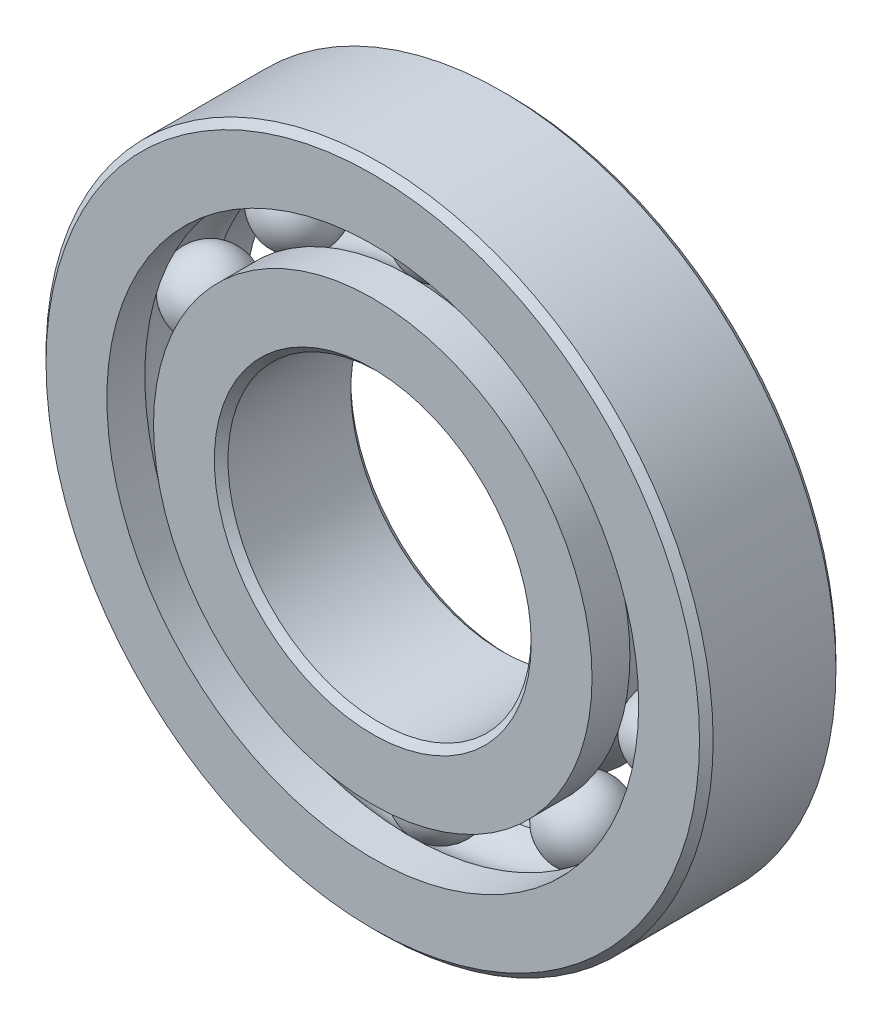
SolidWorks part; units mm, degrees
ref_plane "Front Plane" through (0, 0, 0) normal (0, 0, 1) x (1, 0, 0)
ref_plane "Top Plane" through (0, 0, 0) normal (0, 1, 0) x (1, 0, 0)
ref_plane "Right Plane" through (0, 0, 0) normal (1, 0, 0) x (0, 0, -1)
sketch "Sketch1" plane through (0, 0, 0) normal (1, 0, 0) x (0, 0, -1)
  line L0 (-3.5719, 0) -> (3.5719, 0) construction
  line L1 (0, 17.4625) -> (0, -17.4625) construction
  line L2 (3.2147, 17.4625) -> (-3.2147, 17.4625)
  line L3 (-3.2147, 17.4625) -> (-3.5719, 17.1053)
  line L4 (-3.5719, 17.1053) -> (-3.5719, 13.9212)
  line L5 (-3.5719, 13.9212) -> (-1.5875, 13.9212)
  line L6 (3.5719, 13.9212) -> (1.5875, 13.9212)
  line L7 (3.5719, 17.1053) -> (3.5719, 13.9212)
  line L8 (3.2147, 17.4625) -> (3.5719, 17.1053)
  line L9 (0, 17.4625) -> (0, 12.7) construction
  line L10 (0, 12.7) -> (0, 7.9375) construction
  arc A0 (-1.5875, 13.9212) -> (1.5875, 13.9212) centre (0, 12.7) cw
  point P14 (0, 7.9375)
  dimension "D3" = 3.175
  dimension "D1" = 45
  dimension "Width" = 7.1437
  dimension "OD" = 34.925
  dimension "D2" = 0.3572
  dimension "Shaft Dia" = 15.875
  dimension "D4" = 1.2212
revolve "Revolve1" add sketch "Sketch1" angle 360 about L0
sketch "Sketch3" plane through (0, 0, 0) normal (1, 0, 0) x (0, 0, -1)
  line L0 (-3.5719, 11.4788) -> (-1.5875, 11.4788)
  line L1 (0, 17.4625) -> (0, -17.4625) construction
  line L2 (-3.5719, 17.1053) -> (-3.5719, 13.9212) construction
  line L3 (-3.5719, 11.4788) -> (-3.5719, 8.2947)
  line L4 (-3.2147, 17.4625) -> (-3.5719, 17.1053) construction
  line L5 (-3.5719, 8.2947) -> (-3.2147, 7.9375)
  line L6 (-3.2147, 7.9375) -> (3.2147, 7.9375)
  line L7 (3.2147, 17.4625) -> (3.2147, -17.4625) construction
  line L8 (3.2147, 7.9375) -> (3.5719, 8.2947)
  line L9 (3.5719, -17.1053) -> (3.5719, 17.1053) construction
  line L10 (3.5719, 8.2947) -> (3.5719, 11.4788)
  line L11 (3.5719, 11.4788) -> (1.5875, 11.4788)
  line L13 (3.2147, 17.4625) -> (3.5719, 17.1053) construction
  arc A0 (1.5875, 13.9212) -> (-1.5875, 13.9212) centre (0, 12.7) ccw construction
  arc A1 (1.5875, 11.4788) -> (-1.5875, 11.4788) centre (0, 12.7) cw
revolve "Revolve3" add sketch "Sketch3" angle 360 about L0
sketch "Sketch4" plane through (0, 0, 0) normal (1, 0, 0) x (0, 0, -1)
  line L0 (-2.0028, 12.7) -> (2.0028, 12.7)
  arc A2 (-2.0028, 12.7) -> (2.0028, 12.7) centre (0, 12.7) cw
  arc A3 (1.5875, 13.9212) -> (-1.5875, 13.9212) centre (0, 12.7) ccw construction
revolve "Revolve4" add sketch "Sketch4" angle 360 about L0
ref_axis "Axis1" through (0, 0, -3.5719) along (0, 0, 1)
pattern_circular "CirPattern1" count 10 every 36 about axis through (0, 0, -3.5719) along (0, 0, 1) of bodies 104
sketch "Sketch5" plane through (0, 0, 0) normal (1, 0, 0) x (0, 0, -1)
  line L0 (-3.5719, 13.9212) -> (-1.5875, 13.9212) construction
  line L1 (-3.3933, 13.9212) -> (-2.0028, 13.9212)
  line L2 (-3.3933, 13.9212) -> (-3.3933, 11.4788)
  line L3 (-3.3933, 11.4788) -> (-2.0028, 11.4788)
  line L4 (-2.0028, 13.9212) -> (-2.0028, 11.4788)
  line L5 (-3.5719, 11.4788) -> (-1.5875, 11.4788) construction
  line L6 (3.5719, 13.9212) -> (1.5875, 13.9212) construction
  line L7 (3.3933, 13.9212) -> (2.0028, 13.9212)
  line L8 (3.3933, 13.9212) -> (3.3933, 11.4788)
  line L9 (3.3933, 11.4788) -> (2.0028, 11.4788)
  line L10 (2.0028, 13.9212) -> (2.0028, 11.4788)
  line L11 (3.5719, 11.4788) -> (1.5875, 11.4788) construction
  line L12 (-3.2147, 17.4625) -> (-3.5719, 17.1053) construction
  point P18 (-3.3933, 17.2839)
revolve "Revolve5" [suppressed] add sketch "Sketch5" angle 360 about L0
equation "\"D2@Sketch1\" = \"Width@Sketch1\"*.05"
equation "\"D3@Sketch1\" = \"Width@Sketch1\"/2.25"
equation "\"D4@Sketch1\" = (((\"OD@Sketch1\"-\"Width@Sketch1\")/2)/3.25)/3.5"
equation "\"D2@CirPattern1\" = 360/\"Balls@CirPattern1\""
